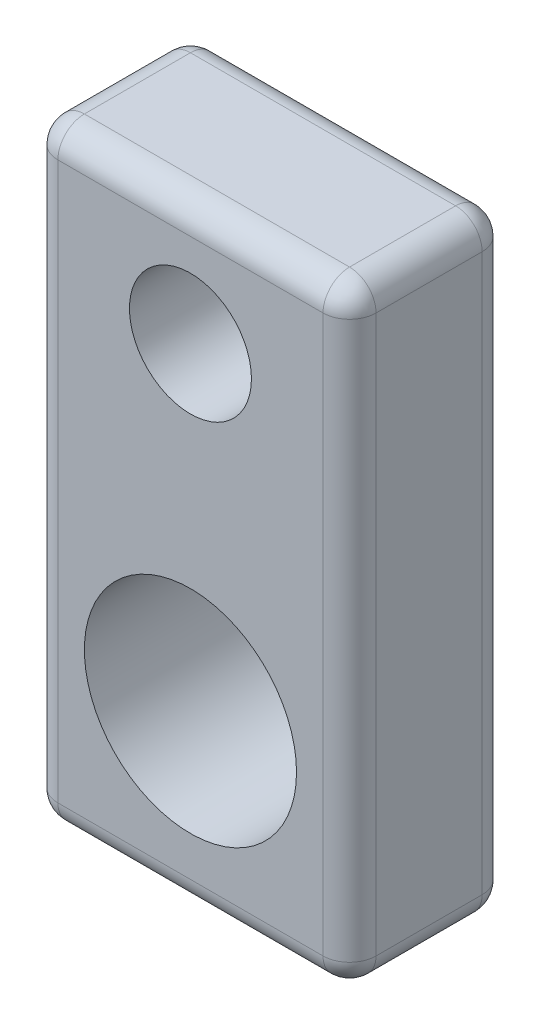
SolidWorks part; units mm, degrees
ref_plane "Front Plane" through (0, 0, 0) normal (0, 0, 1) x (1, 0, 0)
ref_plane "Top Plane" through (0, 0, 0) normal (0, 1, 0) x (1, 0, 0)
ref_plane "Right Plane" through (0, 0, 0) normal (1, 0, 0) x (0, 0, -1)
sketch "Sketch1" plane through (0, 0, 0) normal (0, 0, 1) x (1, 0, 0)
  line L1 (0, 0) -> (12, 0)
  line L2 (0, 0) -> (0, 23)
  line L3 (0, 23) -> (12, 23)
  line L4 (12, 0) -> (12, 23)
  dimension "D1" = 12
  dimension "D2" = 23
extrude "Boss-Extrude1" add sketch "Sketch1" along normal blind 6
sketch "Sketch2" plane through (0, 0, 6) normal (0, 0, 1) x (1, 0, 0)
  line L0 (0, 23) -> (0, 0) construction
  line L1 (12, 23) -> (0, 23) construction
  circle A0 centre (6, 18.5) radius 2.3
  circle A1 centre (6, 6.5) radius 4
  dimension "D1" = 12
  dimension "D2" = 6
  dimension "D3" = 4.6
  dimension "D4" = 4.5
  dimension "D5" = 8
  dimension "D6" = 6
extrude "Cut-Extrude1" cut sketch "Sketch2" against normal blind 6
fillet "Fillet1" radius 1 12 edges at (6, 0, 6) (6, 0, 0) (0, 11.5, 6) (0, 0, 3) (0, 11.5, 0) (6, 23, 6) (0, 23, 3) (6, 23, 0) (12, 0, 3) (12, 11.5, 6) (12, 23, 3) (12, 11.5, 0)
